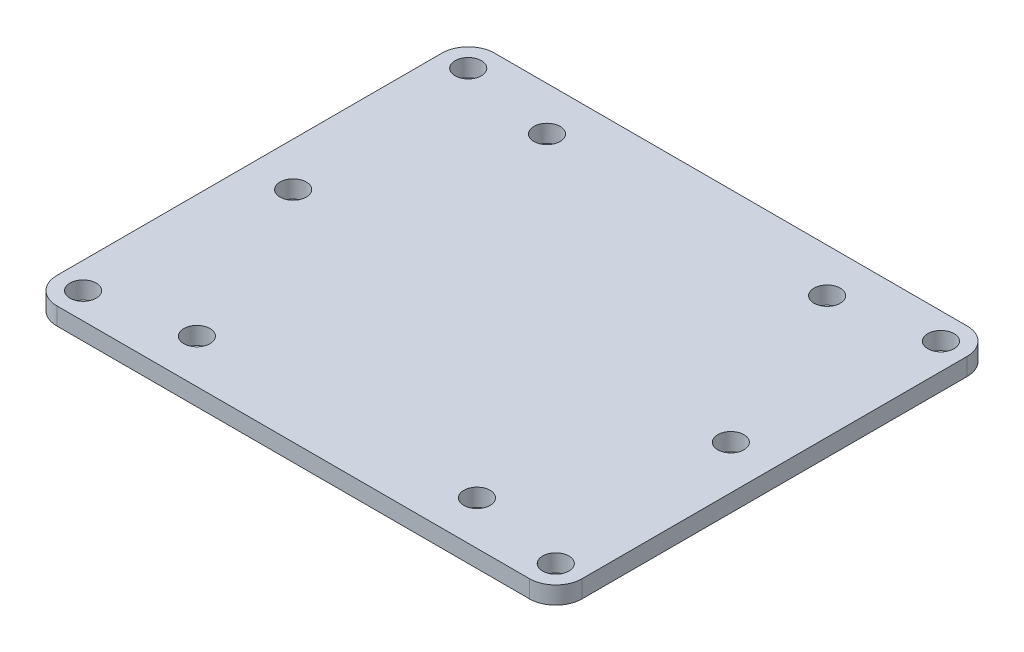
SolidWorks part; units mm, degrees
material "Thornel Mat VMA"
ref_plane "前视基准面" through (0, 0, 0) normal (0, 0, 1) x (1, 0, 0)
ref_plane "上视基准面" through (0, 0, 0) normal (0, 1, 0) x (1, 0, 0)
ref_plane "右视基准面" through (0, 0, 0) normal (1, 0, 0) x (0, 0, -1)
other "Configuration Table"
sketch "草图1" plane through (0, 0, 0) normal (0, 1, 0) x (1, 0, 0)
  line L1 (-30, -25) -> (30, -25)
  line L2 (-30, -25) -> (-30, 25)
  line L3 (-30, 25) -> (30, 25)
  line L4 (30, -25) -> (30, 25)
  line L5 (0, 25) -> (0, -25) construction
  line L6 (-30, 0) -> (30, 0) construction
  point P0 (0, 0)
  dimension "D1" = 60
  dimension "D2" = 50
extrude "凸台-拉伸1" add sketch "草图1" along normal blind 2
sketch "草图2" plane through (0, 2, 0) normal (0, 1, 0) x (1, 0, 0)
  line L0 (-1000, 0) -> (49000, 0) construction
  line L1 (0, -1000) -> (0, 49000) construction
  line L5 (-30, 25) -> (-30, -25) construction
  line L6 (30, 25) -> (-30, 25) construction
  circle A0 centre (-16, 20) radius 1.5
  circle A1 centre (-25, 0) radius 1.5
  circle A2 centre (-16, -20) radius 1.5
  circle A3 centre (16, -20) radius 1.5
  circle A4 centre (25, 0) radius 1.5
  circle A5 centre (16, 20) radius 1.5
  circle A6 centre (-27, 22) radius 1.5
  circle A7 centre (-27, -22) radius 1.5
  circle A8 centre (27, -22) radius 1.5
  circle A9 centre (27, 22) radius 1.5
  dimension "D1" = 25
  dimension "D2" = 3
  dimension "D3" = 3
  dimension "D4" = 16
  dimension "D5" = 20
  dimension "D6" = 3
  dimension "D7" = 3
  dimension "D8" = 3
extrude "切除-拉伸1" cut sketch "草图2" against normal through all
fillet "圆角1" radius 3 4 edges at (-30, 1, 25) (30, 1, 25) (30, 1, -25) (-30, 1, -25)
